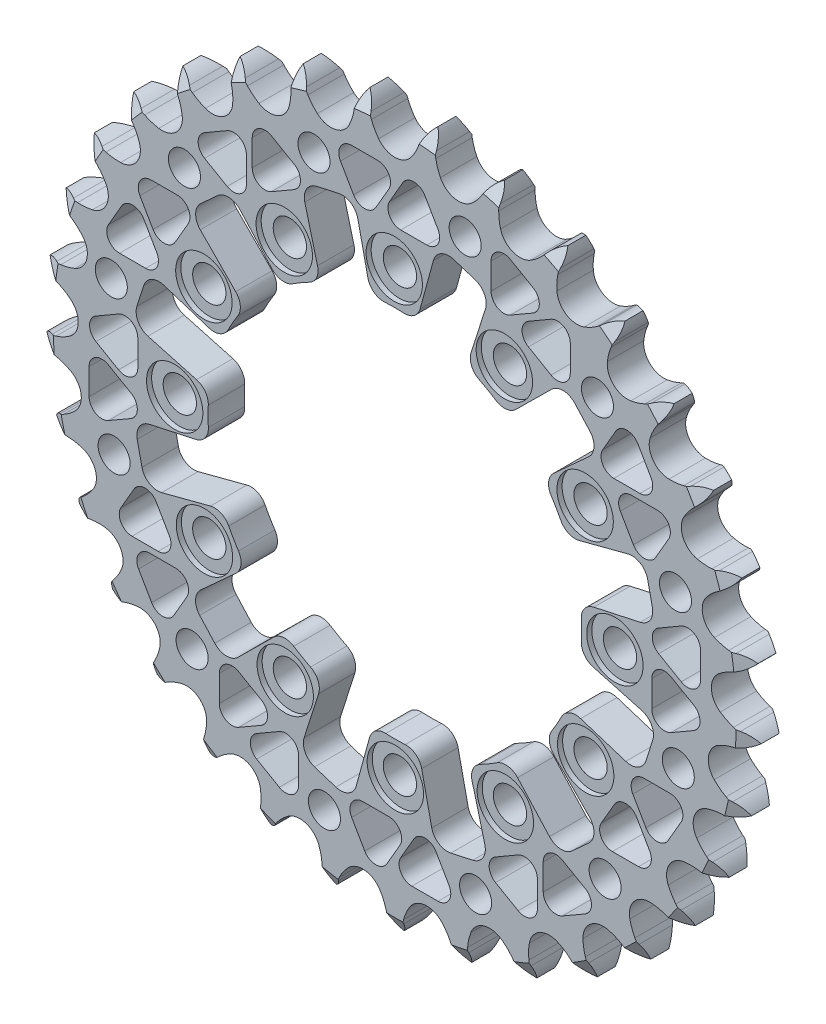
SolidWorks part; units mm, degrees
other "Markup1"
sketch "Sketch16" plane through (70.768, -70.8482, 7.2136) normal (0.1919, -0.04, 0.9806) x (0.9727, -0.1249, -0.1954)
material "7075-T6 (SN)"
ref_plane "Front Plane" through (0, 0, 0) normal (0, 0, 1) x (1, 0, 0)
ref_plane "Top Plane" through (0, 0, 0) normal (0, 1, 0) x (1, 0, 0)
ref_plane "Right Plane" through (0, 0, 0) normal (1, 0, 0) x (0, 0, -1)
sketch "Work Sketch" plane through (0, 0, 0) normal (0, 0, 1) x (1, 0, 0)
  line L0 (0, 0) -> (0, 160.4542) construction
  line L1 (-112.0919, 66.8027) -> (87.2579, 66.8027) construction
  line L2 (5.0834, 120.8822) -> (5.0834, 112.9699) construction
  line L3 (-12.8497, 70.6081) -> (16.7256, 70.6081) construction
  line L4 (5.0834, 70.6081) -> (-6.0658, 62.2619) construction
  line L5 (5.0834, 70.6081) -> (-4.6352, 66.9715) construction
  line L6 (-4.6352, 66.9715) -> (-6.998, 73.2861)
  line L7 (-11.5114, 65.7464) -> (-7.1525, 65.7464) construction
  line L8 (-11.0622, 124.7602) -> (-11.0622, 110.2345) construction
  line L9 (0, 0) -> (-4.0639, 42.5596) construction
  circle A0 centre (0, 0) radius 66.8027
  circle A1 centre (0, 66.8027) radius 4.0088
  arc A2 (-4.6352, 66.9715) -> (-3.2092, 64.4003) centre (5.0609, 70.6677) ccw
  circle A3 centre (-11.0622, 65.7464) radius 6.4488
  point P23 (-3.2092, 64.4003)
  dimension "D1" = 133.6054
  dimension "D8" = 10.3767
  dimension "D2" = 8.0177
  dimension "D3" = 5.0834
  dimension "D4" = 3.8054
  dimension "D5" = 36.818
  dimension "D6" = 16.303
  dimension "D7" = 10.3767
  dimension "D9" = 1.0563
  dimension "D10" = 11.0622
  dimension "D11" = 5.455
sketch "Teeth Sketch" plane through (0, 0, 0) normal (0, 0, 1) x (1, 0, 0)
  line L0 (5.0224, 68.0064) -> (4.6352, 66.9715)
  line L1 (-8.8439, 92.6176) -> (-5.6513, 59.1829) construction
  line L2 (0, 0) -> (-12.8498, 132.1321) construction
  line L3 (7.9387, 67.7279) -> (8.123, 66.6385)
  line L4 (19011.2087, -199094.3845) -> (-19015.2726, 199136.9441) construction
  line L5 (0, 146.3285) -> (0, 56.9858) construction
  line L6 (17.8019, 65.8269) -> (17.2258, 64.8841)
  line L7 (0, -200000) -> (0, 200160.4542) construction
  line L8 (20.6128, 65.0016) -> (20.5877, 63.897)
  line L9 (-4.6352, 66.9715) -> (-6.998, 73.2861) construction
  line L10 (43.2949, 52.6844) -> (42.861, 51.6682)
  line L11 (-5.0224, 68.0064) -> (-4.6352, 66.9715)
  line L12 (29.938, 61.2683) -> (29.1939, 60.4515)
  line L13 (32.5419, 59.9259) -> (32.3082, 58.846)
  line L14 (40.9921, 54.4953) -> (40.1069, 53.8341)
  line L15 (50.5647, 45.7527) -> (49.5703, 45.271)
  line L16 (52.4831, 43.5387) -> (51.8648, 42.623)
  line L17 (58.3096, 35.3565) -> (57.2421, 35.0716)
  line L18 (59.7744, 32.8194) -> (58.9939, 32.0373)
  line L19 (63.9472, 23.6824) -> (62.845, 23.6047)
  line L20 (64.9053, 20.9139) -> (63.9909, 20.2936)
  line L21 (67.2735, 11.1523) -> (66.1765, 11.2846)
  line L22 (67.6904, 8.2526) -> (66.6751, 7.8165)
  line L23 (68.1683, -1.7808) -> (67.1162, -1.4433)
  line L24 (68.0289, -4.7071) -> (66.9495, -4.9431)
  line L25 (66.5994, -14.6496) -> (65.6302, -14.119)
  line L26 (65.9088, -17.4966) -> (64.8042, -17.524)
  line L27 (62.6234, -26.9889) -> (61.7722, -26.2845)
  line L28 (61.4065, -29.6537) -> (60.3166, -29.4716)
  line L29 (56.3841, -38.3527) -> (55.6815, -37.4999)
  line L30 (54.6848, -40.739) -> (53.6491, -40.354)
  line L31 (48.1068, -48.3304) -> (47.5783, -47.3601)
  line L32 (45.9866, -50.352) -> (45.0425, -49.7779)
  line L33 (38.0909, -56.5613) -> (37.7556, -55.5085)
  line L34 (35.6264, -58.1451) -> (34.808, -57.4027)
  line L35 (26.6983, -62.7479) -> (26.5682, -61.6506)
  line L36 (23.9786, -63.8367) -> (23.3155, -62.9529)
  line L37 (14.3407, -66.6666) -> (14.4207, -65.5646)
  line L38 (11.4641, -67.221) -> (10.9802, -66.2277)
  line L39 (1.4648, -68.1759) -> (1.7519, -67.1089)
  line L40 (-1.4648, -68.1759) -> (-1.7519, -67.1089)
  line L41 (-11.4641, -67.221) -> (-10.9802, -66.2277)
  line L42 (-14.3407, -66.6666) -> (-14.4207, -65.5646)
  line L43 (-23.9786, -63.8367) -> (-23.3155, -62.9529)
  line L44 (-26.6983, -62.7479) -> (-26.5682, -61.6506)
  line L45 (-35.6264, -58.1451) -> (-34.808, -57.4027)
  line L46 (-38.0909, -56.5613) -> (-37.7556, -55.5085)
  line L47 (-45.9866, -50.352) -> (-45.0425, -49.7779)
  line L48 (-48.1068, -48.3304) -> (-47.5783, -47.3601)
  line L49 (-54.6848, -40.739) -> (-53.6491, -40.354)
  line L50 (-56.3841, -38.3527) -> (-55.6815, -37.4999)
  line L51 (-61.4065, -29.6537) -> (-60.3166, -29.4716)
  line L52 (-62.6234, -26.9889) -> (-61.7722, -26.2845)
  line L53 (-65.9088, -17.4966) -> (-64.8042, -17.524)
  line L54 (-66.5994, -14.6496) -> (-65.6302, -14.119)
  line L55 (-68.0289, -4.7071) -> (-66.9495, -4.9431)
  line L56 (-68.1683, -1.7808) -> (-67.1162, -1.4433)
  line L57 (-67.6904, 8.2526) -> (-66.6751, 7.8165)
  line L58 (-67.2735, 11.1523) -> (-66.1765, 11.2846)
  line L59 (-64.9053, 20.9139) -> (-63.9909, 20.2936)
  line L60 (-63.9472, 23.6824) -> (-62.845, 23.6047)
  line L61 (-59.7744, 32.8194) -> (-58.9939, 32.0373)
  line L62 (-58.3096, 35.3565) -> (-57.2421, 35.0716)
  line L63 (-52.4831, 43.5387) -> (-51.8648, 42.623)
  line L64 (-50.5647, 45.7527) -> (-49.5703, 45.271)
  line L65 (-43.2949, 52.6844) -> (-42.861, 51.6682)
  line L66 (-40.9921, 54.4953) -> (-40.1069, 53.8341)
  line L67 (-32.5419, 59.9259) -> (-32.3082, 58.846)
  line L68 (-29.938, 61.2683) -> (-29.1939, 60.4515)
  line L69 (-20.6128, 65.0016) -> (-20.5877, 63.897)
  line L70 (-17.8019, 65.8269) -> (-17.2258, 64.8841)
  line L71 (-7.9387, 67.7279) -> (-8.123, 66.6385)
  arc A0 (-6.8704, 70.647) -> (-5.0224, 68.0064) centre (-11.0622, 65.7464) cw
  circle A1 centre (-11.0622, 65.7464) radius 6.4488 construction
  arc A2 (-3.2092, 64.4003) -> (-4.6352, 66.9715) centre (5.0609, 70.6677) cw
  arc A3 (-4.6352, 66.9715) -> (-3.2092, 64.4003) centre (5.0609, 70.6677) ccw construction
  circle A4 centre (0, 66.8027) radius 4.0088 construction
  arc A5 (-3.2092, 64.4003) -> (3.2092, 64.4003) centre (0, 66.8027) ccw
  arc A6 (3.2092, 64.4003) -> (4.6352, 66.9715) centre (-5.0609, 70.6677) ccw
  arc A7 (6.8704, 70.647) -> (5.0224, 68.0064) centre (11.0622, 65.7464) ccw
  arc A8 (6.6238, 70.6705) -> (7.9387, 67.7279) centre (1.5803, 66.6518) cw
  arc A9 (9.0366, 63.8438) -> (8.123, 66.6385) centre (18.3434, 68.4328) cw
  arc A10 (9.0366, 63.8438) -> (15.3391, 62.6291) centre (12.6425, 65.5955) ccw
  arc A11 (15.3391, 62.6291) -> (17.2258, 64.8841) centre (8.4044, 70.3484) ccw
  arc A12 (20.1163, 68.0701) -> (17.8019, 65.8269) centre (23.3049, 62.4647) ccw
  arc A13 (19.8786, 68.1399) -> (20.6128, 65.0016) centre (14.1657, 65.1482) cw
  arc A14 (20.9558, 60.9799) -> (20.5877, 63.897) centre (30.9629, 63.7246) cw
  arc A15 (20.9558, 60.9799) -> (26.9145, 58.5944) centre (24.8281, 62.0175) ccw
  arc A16 (26.9145, 58.5944) -> (29.1939, 60.4515) centre (21.5661, 67.4865) ccw
  arc A17 (32.6351, 63.0329) -> (29.938, 61.2683) centre (34.7052, 56.9254) ccw
  arc A18 (32.4149, 63.1465) -> (32.5419, 59.9259) centre (26.2391, 61.29) cw
  arc A19 (32.1176, 55.912) -> (32.3082, 58.846) centre (42.4634, 56.7133) cw
  arc A20 (32.1176, 55.912) -> (37.5172, 52.4419) centre (36.1163, 56.198) ccw
  arc A21 (37.5172, 52.4419) -> (40.1069, 53.8341) centre (33.9483, 62.1856) ccw
  arc A22 (43.9744, 55.7176) -> (40.9921, 54.4953) centre (44.8513, 49.3287) ccw
  arc A23 (43.7796, 55.8708) -> (43.2949, 52.6844) centre (37.3641, 55.2167) cw
  arc A24 (42.1187, 48.8233) -> (42.861, 51.6682) centre (52.429, 47.6521) cw
  arc A25 (42.1187, 48.8233) -> (46.7639, 44.3941) centre (46.0991, 48.3474) ccw
  arc A26 (46.7639, 44.3941) -> (49.5703, 45.271) centre (45.1035, 54.637) ccw
  arc A27 (53.7244, 46.3885) -> (50.5647, 45.7527) centre (53.3763, 39.9491) ccw
  arc A28 (53.5621, 46.5757) -> (52.4831, 43.5387) centre (47.1387, 47.1476) cw
  arc A29 (50.5974, 39.97) -> (51.8648, 42.623) centre (60.4998, 36.8687) cw
  arc A30 (50.5974, 39.97) -> (54.3205, 34.7417) centre (54.4159, 38.7494) ccw
  arc A31 (54.3205, 34.7417) -> (57.2421, 35.0716) centre (54.6285, 45.1138) ccw
  arc A32 (61.5326, 35.3828) -> (58.3096, 35.3565) centre (59.9721, 29.1257) ccw
  arc A33 (61.4087, 35.5974) -> (59.7744, 32.8194) centre (55.2096, 37.3746) cw
  arc A34 (57.2474, 29.6721) -> (58.9939, 32.0373) centre (66.384, 24.7528) cw
  arc A35 (57.2474, 29.6721) -> (59.9137, 23.8336) centre (60.7659, 27.7508) ccw
  arc A36 (59.9137, 23.8336) -> (62.845, 23.6047) centre (62.1792, 33.96) ccw
  arc A37 (67.1168, 23.0983) -> (63.9472, 23.6824) centre (64.4004, 17.2495) ccw
  arc A38 (67.0358, 23.3324) -> (64.9053, 20.9139) centre (61.2851, 26.2507) cw
  arc A39 (61.8283, 18.3017) -> (63.9909, 20.2936) centre (69.8688, 11.7422) cw
  arc A40 (61.8283, 18.3017) -> (63.3416, 12.0642) centre (64.9196, 15.7493) ccw
  arc A41 (63.3416, 12.0642) -> (66.1765, 11.2846) centre (67.4825, 21.5788) ccw
  arc A42 (70.2753, 9.9789) -> (67.2735, 11.1523) centre (66.5011, 4.7499) ccw
  arc A43 (70.2401, 10.2242) -> (67.6904, 8.2526) centre (65.1456, 14.178) cw
  arc A44 (64.1746, 6.2699) -> (66.6751, 7.8165) centre (70.8284, -1.6927) cw
  arc A45 (64.1746, 6.2699) -> (64.48, -0.1413) centre (66.727, 3.1786) ccw
  arc A46 (64.48, -0.1413) -> (67.1162, -1.4433) centre (70.3468, 8.4177) ccw
  arc A47 (70.8939, -3.5011) -> (68.1683, -1.7808) centre (66.1983, -7.9213) ccw
  arc A48 (70.9057, -3.2536) -> (68.0289, -4.7071) centre (66.6515, 1.5929) cw
  arc A49 (64.2015, -5.9885) -> (66.9495, -4.9431) centre (69.2281, -15.0665) cw
  arc A50 (64.2015, -5.9885) -> (63.2881, -12.3417) centre (66.1227, -9.507) ccw
  arc A51 (63.2881, -12.3417) -> (65.6302, -14.119) centre (70.6686, -5.0476) ccw
  arc A52 (68.9501, -16.8546) -> (66.5994, -14.6496) centre (63.5029, -20.3063) ccw
  arc A53 (69.0085, -16.6138) -> (65.9088, -17.4966) centre (65.7485, -11.0498) cw
  arc A54 (61.908, -18.0305) -> (64.8042, -17.524) centre (65.1257, -27.8957) cw
  arc A55 (61.908, -18.0305) -> (59.8087, -24.096) centre (63.1286, -21.849) ccw
  arc A56 (59.8087, -24.096) -> (61.7722, -26.2845) centre (68.4363, -18.3305) ccw
  arc A57 (64.5144, -29.5989) -> (62.6234, -26.9889) centre (58.5123, -31.9573) ccw
  arc A58 (64.6173, -29.3735) -> (61.4065, -29.6537) centre (62.4691, -23.2931) cw
  arc A59 (57.3769, -29.4209) -> (60.3166, -29.4716) centre (58.6695, -39.7167) cw
  arc A60 (57.3769, -29.4209) -> (54.1677, -34.9794) centre (57.8528, -33.4013) ccw
  arc A61 (54.1677, -34.9794) -> (55.6815, -37.4999) centre (63.7305, -30.9509) ccw
  arc A62 (57.7469, -41.2734) -> (56.3841, -38.3527) centre (51.4069, -42.4533) ccw
  arc A63 (57.8906, -41.0716) -> (54.6848, -40.739) centre (56.932, -34.6945) cw
  arc A64 (50.7721, -39.7478) -> (53.6491, -40.354) centre (50.0928, -50.1023) cw
  arc A65 (50.7721, -39.7478) -> (46.5689, -44.5986) centre (50.4861, -43.7465) ccw
  arc A66 (46.5689, -44.5986) -> (47.5783, -47.3601) centre (56.7213, -42.4527) ccw
  arc A67 (48.8923, -51.4562) -> (48.1068, -48.3304) centre (42.4436, -51.415) ccw
  arc A68 (49.0716, -51.2853) -> (45.9866, -50.352) centre (49.3372, -44.842) cw
  arc A69 (42.3322, -48.6382) -> (45.0425, -49.7779) centre (39.7057, -58.677) cw
  arc A70 (42.3322, -48.6382) -> (37.287, -52.6059) centre (41.2947, -52.5105) ccw
  arc A71 (37.287, -52.6059) -> (37.7556, -55.5085) centre (47.662, -52.4201) ccw
  arc A72 (38.2706, -59.7793) -> (38.0909, -56.5613) centre (31.9463, -58.5183) ccw
  arc A73 (38.479, -59.6453) -> (35.6264, -58.1451) centre (39.9592, -53.3687) cw
  arc A74 (32.3624, -55.7707) -> (34.808, -57.4027) centre (27.8834, -65.131) cw
  arc A75 (32.3624, -55.7707) -> (26.6574, -58.7118) centre (30.6108, -59.3766) ccw
  arc A76 (26.6574, -58.7118) -> (26.5682, -61.6506) centre (36.8801, -60.4929) ccw
  arc A77 (26.2657, -65.9417) -> (26.6983, -62.7479) centre (20.2943, -63.5067) ccw
  arc A78 (26.4957, -65.8497) -> (23.9786, -63.8367) centre (29.137, -59.9666) cw
  arc A79 (21.2229, -60.8875) -> (23.3155, -62.9529) centre (15.0534, -69.2309) cw
  arc A80 (21.2229, -60.8875) -> (15.0644, -62.6958) centre (18.8205, -64.0967) ccw
  arc A81 (15.0644, -62.6958) -> (14.4207, -65.5646) centre (24.7653, -66.3793) ccw
  arc A82 (13.3114, -69.7209) -> (14.3407, -66.6666) centre (7.9088, -66.1998) ccw
  arc A83 (13.5547, -69.674) -> (11.4641, -67.221) centre (17.2617, -64.3972) cw
  arc A84 (9.3163, -63.8036) -> (10.9802, -66.2277) centre (1.6794, -70.8287) cw
  arc A85 (9.3163, -63.8036) -> (2.9269, -64.4137) centre (6.35, -66.5002) ccw
  arc A86 (2.9269, -64.4137) -> (1.7519, -67.1089) centre (11.7554, -69.8666) ccw
  arc A87 (-0.1239, -70.9802) -> (1.4648, -68.1759) centre (-4.7625, -66.5002) ccw
  arc A88 (0.1239, -70.9802) -> (-1.4648, -68.1759) centre (4.7625, -66.5002) cw
  arc A89 (-2.9269, -64.4137) -> (-1.7519, -67.1089) centre (-11.7554, -69.8666) cw
  arc A90 (-2.9269, -64.4137) -> (-9.3163, -63.8036) centre (-6.35, -66.5002) ccw
  arc A91 (-9.3163, -63.8036) -> (-10.9802, -66.2277) centre (-1.6794, -70.8287) ccw
  arc A92 (-13.5547, -69.674) -> (-11.4641, -67.221) centre (-17.2617, -64.3972) ccw
  arc A93 (-13.3114, -69.7209) -> (-14.3407, -66.6666) centre (-7.9088, -66.1998) cw
  arc A94 (-15.0644, -62.6958) -> (-14.4207, -65.5646) centre (-24.7653, -66.3793) cw
  arc A95 (-15.0644, -62.6958) -> (-21.2229, -60.8875) centre (-18.8205, -64.0967) ccw
  arc A96 (-21.2229, -60.8875) -> (-23.3155, -62.9529) centre (-15.0534, -69.2309) ccw
  arc A97 (-26.4957, -65.8497) -> (-23.9786, -63.8367) centre (-29.137, -59.9666) ccw
  arc A98 (-26.2657, -65.9417) -> (-26.6983, -62.7479) centre (-20.2943, -63.5067) cw
  arc A99 (-26.6574, -58.7118) -> (-26.5682, -61.6506) centre (-36.8801, -60.4929) cw
  arc A100 (-26.6574, -58.7118) -> (-32.3624, -55.7707) centre (-30.6108, -59.3766) ccw
  arc A101 (-32.3624, -55.7707) -> (-34.808, -57.4027) centre (-27.8834, -65.131) ccw
  arc A102 (-38.479, -59.6453) -> (-35.6264, -58.1451) centre (-39.9592, -53.3687) ccw
  arc A103 (-38.2706, -59.7793) -> (-38.0909, -56.5613) centre (-31.9463, -58.5183) cw
  arc A104 (-37.287, -52.6059) -> (-37.7556, -55.5085) centre (-47.662, -52.4201) cw
  arc A105 (-37.287, -52.6059) -> (-42.3322, -48.6382) centre (-41.2947, -52.5105) ccw
  arc A106 (-42.3322, -48.6382) -> (-45.0425, -49.7779) centre (-39.7057, -58.677) ccw
  arc A107 (-49.0716, -51.2853) -> (-45.9866, -50.352) centre (-49.3372, -44.842) ccw
  arc A108 (-48.8923, -51.4562) -> (-48.1068, -48.3304) centre (-42.4436, -51.415) cw
  arc A109 (-46.5689, -44.5986) -> (-47.5783, -47.3601) centre (-56.7213, -42.4527) cw
  arc A110 (-46.5689, -44.5986) -> (-50.7721, -39.7478) centre (-50.4861, -43.7465) ccw
  arc A111 (-50.7721, -39.7478) -> (-53.6491, -40.354) centre (-50.0928, -50.1023) ccw
  arc A112 (-57.8906, -41.0716) -> (-54.6848, -40.739) centre (-56.932, -34.6945) ccw
  arc A113 (-57.7469, -41.2734) -> (-56.3841, -38.3527) centre (-51.4069, -42.4533) cw
  arc A114 (-54.1677, -34.9794) -> (-55.6815, -37.4999) centre (-63.7305, -30.9509) cw
  arc A115 (-54.1677, -34.9794) -> (-57.3769, -29.4209) centre (-57.8528, -33.4013) ccw
  arc A116 (-57.3769, -29.4209) -> (-60.3166, -29.4716) centre (-58.6695, -39.7167) ccw
  arc A117 (-64.6173, -29.3735) -> (-61.4065, -29.6537) centre (-62.4691, -23.2931) ccw
  arc A118 (-64.5144, -29.5989) -> (-62.6234, -26.9889) centre (-58.5123, -31.9573) cw
  arc A119 (-59.8087, -24.096) -> (-61.7722, -26.2845) centre (-68.4363, -18.3305) cw
  arc A120 (-59.8087, -24.096) -> (-61.908, -18.0305) centre (-63.1286, -21.849) ccw
  arc A121 (-61.908, -18.0305) -> (-64.8042, -17.524) centre (-65.1257, -27.8957) ccw
  arc A122 (-69.0085, -16.6138) -> (-65.9088, -17.4966) centre (-65.7485, -11.0498) ccw
  arc A123 (-68.9501, -16.8546) -> (-66.5994, -14.6496) centre (-63.5029, -20.3063) cw
  arc A124 (-63.2881, -12.3417) -> (-65.6302, -14.119) centre (-70.6686, -5.0476) cw
  arc A125 (-63.2881, -12.3417) -> (-64.2015, -5.9885) centre (-66.1227, -9.507) ccw
  arc A126 (-64.2015, -5.9885) -> (-66.9495, -4.9431) centre (-69.2281, -15.0665) ccw
  arc A127 (-70.9057, -3.2536) -> (-68.0289, -4.7071) centre (-66.6515, 1.5929) ccw
  arc A128 (-70.8939, -3.5011) -> (-68.1683, -1.7808) centre (-66.1983, -7.9213) cw
  arc A129 (-64.48, -0.1413) -> (-67.1162, -1.4433) centre (-70.3468, 8.4177) cw
  arc A130 (-64.48, -0.1413) -> (-64.1746, 6.2699) centre (-66.727, 3.1786) ccw
  arc A131 (-64.1746, 6.2699) -> (-66.6751, 7.8165) centre (-70.8284, -1.6927) ccw
  arc A132 (-70.2401, 10.2242) -> (-67.6904, 8.2526) centre (-65.1456, 14.178) ccw
  arc A133 (-70.2753, 9.9789) -> (-67.2735, 11.1523) centre (-66.5011, 4.7499) cw
  arc A134 (-63.3416, 12.0642) -> (-66.1765, 11.2846) centre (-67.4825, 21.5788) cw
  arc A135 (-63.3416, 12.0642) -> (-61.8283, 18.3017) centre (-64.9196, 15.7493) ccw
  arc A136 (-61.8283, 18.3017) -> (-63.9909, 20.2936) centre (-69.8688, 11.7422) ccw
  arc A137 (-67.0358, 23.3324) -> (-64.9053, 20.9139) centre (-61.2851, 26.2507) ccw
  arc A138 (-67.1168, 23.0983) -> (-63.9472, 23.6824) centre (-64.4004, 17.2495) cw
  arc A139 (-59.9137, 23.8336) -> (-62.845, 23.6047) centre (-62.1792, 33.96) cw
  arc A140 (-59.9137, 23.8336) -> (-57.2474, 29.6721) centre (-60.7659, 27.7508) ccw
  arc A141 (-57.2474, 29.6721) -> (-58.9939, 32.0373) centre (-66.384, 24.7528) ccw
  arc A142 (-61.4087, 35.5974) -> (-59.7744, 32.8194) centre (-55.2096, 37.3746) ccw
  arc A143 (-61.5326, 35.3828) -> (-58.3096, 35.3565) centre (-59.9721, 29.1257) cw
  arc A144 (-54.3205, 34.7417) -> (-57.2421, 35.0716) centre (-54.6285, 45.1138) cw
  arc A145 (-54.3205, 34.7417) -> (-50.5974, 39.97) centre (-54.4159, 38.7494) ccw
  arc A146 (-50.5974, 39.97) -> (-51.8648, 42.623) centre (-60.4998, 36.8687) ccw
  arc A147 (-53.5621, 46.5757) -> (-52.4831, 43.5387) centre (-47.1387, 47.1476) ccw
  arc A148 (-53.7244, 46.3885) -> (-50.5647, 45.7527) centre (-53.3763, 39.9491) cw
  arc A149 (-46.7639, 44.3941) -> (-49.5703, 45.271) centre (-45.1035, 54.637) cw
  arc A150 (-46.7639, 44.3941) -> (-42.1187, 48.8233) centre (-46.0991, 48.3474) ccw
  arc A151 (-42.1187, 48.8233) -> (-42.861, 51.6682) centre (-52.429, 47.6521) ccw
  arc A152 (-43.7796, 55.8708) -> (-43.2949, 52.6844) centre (-37.3641, 55.2167) ccw
  arc A153 (-43.9744, 55.7176) -> (-40.9921, 54.4953) centre (-44.8513, 49.3287) cw
  arc A154 (-37.5172, 52.4419) -> (-40.1069, 53.8341) centre (-33.9483, 62.1856) cw
  arc A155 (-37.5172, 52.4419) -> (-32.1176, 55.912) centre (-36.1163, 56.198) ccw
  arc A156 (-32.1176, 55.912) -> (-32.3082, 58.846) centre (-42.4634, 56.7133) ccw
  arc A157 (-32.4149, 63.1465) -> (-32.5419, 59.9259) centre (-26.2391, 61.29) ccw
  arc A158 (-32.6351, 63.0329) -> (-29.938, 61.2683) centre (-34.7052, 56.9254) cw
  arc A159 (-26.9145, 58.5944) -> (-29.1939, 60.4515) centre (-21.5661, 67.4865) cw
  arc A160 (-26.9145, 58.5944) -> (-20.9558, 60.9799) centre (-24.8281, 62.0175) ccw
  arc A161 (-20.9558, 60.9799) -> (-20.5877, 63.897) centre (-30.9629, 63.7246) ccw
  arc A162 (-19.8786, 68.1399) -> (-20.6128, 65.0016) centre (-14.1657, 65.1482) ccw
  arc A163 (-20.1163, 68.0701) -> (-17.8019, 65.8269) centre (-23.3049, 62.4647) cw
  arc A164 (-15.3391, 62.6291) -> (-17.2258, 64.8841) centre (-8.4044, 70.3484) cw
  arc A165 (-15.3391, 62.6291) -> (-9.0366, 63.8438) centre (-12.6425, 65.5955) ccw
  arc A166 (-9.0366, 63.8438) -> (-8.123, 66.6385) centre (-18.3434, 68.4328) ccw
  arc A167 (-6.6238, 70.6705) -> (-7.9387, 67.7279) centre (-1.5803, 66.6518) ccw
  point P77 (0, 0)
  dimension "D1" = 5.455
  dimension "D2" = 5.555
  dimension "D3" = 33
extrude "Extrusion" add sketch "Teeth Sketch" along normal blind 7.2136
hole_wizard "M6 Clearance Hole1" positions "Sketch6" profile "Sketch7" hole size "M6" standard "ANSI Metric"
sketch "Sketch6" plane through (0, 0, 0) normal (0, 0, -1) x (-1, 0, 0)
  circle A0 centre (0, 0) radius 43.5
  point P0 (0, 43.5)
  dimension "D1" = 87
sketch "Sketch7" plane through (0, 43.5, 0) normal (1, 0, 0) x (0, 1, 0)
  line L0 (0, 0) -> (0, 19.2548)
  line L1 (0, 19.2548) -> (3.3, 17.272)
  line L2 (3.3, 17.272) -> (3.3, 0)
  line L5 (3.3, 0) -> (0, 0)
  line L10 (0, 19.2548) -> (-3.3, 17.272) construction
  line L11 (0, -6.35) -> (0, 107.95) construction
  dimension "Hole Dia." = 6.6
  dimension "Hole Depth" = 17.272
  dimension "Drill Angle" = 118
pattern_circular "CirPattern1" count 12 over 360 about axis through (0, -0.1107, 0) along (0, 0, 1) of "M6 Clearance Hole1"
sketch "Sketch8" plane through (0, 0, 0) normal (0, 0, -1) x (-1, 0, 0)
  circle A0 centre (0, 0) radius 37
  dimension "D1" = 74
extrude "Cut-Extrude1" cut sketch "Sketch8" against normal through all both and the other way through all
ref_plane "Sprocket Center Plane" through (0, 0, 3.6068) normal (0, 0, 1) x (1, 0, 0)
sketch "Pitch Circle" plane through (0, 0, 3.6068) normal (0, 0, -1) x (-1, 0, 0)
  circle A0 centre (0, 0) radius 66.8027 construction
  dimension "D1" = 133.6054
ref_plane "Center Plane" through (0, 0, 3.6068) normal (0, 0, 1) x (1, 0, 0)
ref_axis "Axis1" through (0, 0, 7.2136) along (0, 0, -1)
sketch "Sketch5" plane through (0, 0, 0) normal (1, 0, 0) x (0, 0, -1)
  line L0 (-1.8288, -70.8482) -> (-5.3848, -70.8482)
  line L1 (-7.2136, -51.2753) -> (0, -51.2753) construction
  line L2 (-5.3848, -70.8482) -> (-5.3848, -67.6547)
  line L3 (-5.3848, -67.6547) -> (-7.2136, -67.6547)
  line L4 (-7.2136, -67.6547) -> (-5.3848, -70.8482)
  line L5 (-7.2136, -67.6547) -> (-7.2136, -70.8482)
  line L6 (-7.2136, -70.8482) -> (-5.3848, -70.8482)
  line L8 (-7.2136, -70.8482) -> (0, -70.8482) construction
  line L9 (-7.2136, -68.1759) -> (-7.2136, -70.8482) construction
  dimension "D1" = 3.556
  dimension "D2" = 3.1936
  dimension "D3" = 1.8288
revolve "Cut-Revolve1" cut sketch "Sketch5" angle 360 about axis through (0, 0, 7.2136) along (0, 0, -1)
mirror "Mirror1" about plane through (0, 0, 3.6068) normal (0, 0, 1) of "Cut-Revolve1"
sketch "Sketch10" plane through (0, 0, 0) normal (0, 0, 1) x (1, 0, 0)
  line L0 (0, 0) -> (-79.643, -0.2022) construction
  line L1 (0, 0) -> (-79.6429, 10.0842) construction
  line L2 (0, 0) -> (-79.643, -10.4954) construction
  line L3 (-59.2423, 9.0305) -> (-51.4071, 1.075)
  line L5 (-49.1987, 6.2294) -> (-49.1987, 5.0699)
  line L6 (-51.4071, 1.075) -> (-62.5732, 1.075)
  line L8 (-62.7341, -1.6349) -> (-51.5692, -1.4798)
  line L9 (-51.5692, -1.4798) -> (-59.2931, -9.5434)
  line L12 (-49.1987, -0.1249) -> (-49.1987, -0.1107)
  line L15 (-51.5692, -1.4798) -> (-53.764, -1.4798) construction
  line L16 (-51.4071, 1.075) -> (-52.3044, 1.075) construction
  line L17 (-59.2423, 9.0305) -> (-62.5732, 1.075)
  line L18 (-62.7341, -1.6349) -> (-59.2931, -9.5434)
  line L19 (-45.388, 21.6946) -> (-49.1987, 5.0699)
  line L20 (-31.807, 16.9479) -> (-36.0091, 0.4177)
  line L22 (-49.1987, -0.1107) -> (-49.1987, -0.1249)
  line L23 (-49.1987, 5.0699) -> (-49.1987, 6.2294)
  circle A0 centre (-43.6107, -0.1107) radius 5.588
  circle A1 centre (-37.768, 21.6946) radius 5.588
  arc A2 (-36.0091, 0.4177) -> (-49.1987, 5.0699) centre (-43.6107, -0.1107) ccw
  arc A3 (-45.388, 21.6946) -> (-31.807, 16.9479) centre (-37.768, 21.6946) ccw
  dimension "D1" = 11.176
  dimension "D12" = 15.24
  dimension "D2" = 4.8001
  dimension "D3" = 0.7635
  dimension "D4" = 35.8718
  dimension "D6" = 11.165
  dimension "D8" = 2.7099
  dimension "D10" = 11.166
  dimension "D11" = 7.9555
  dimension "D13" = 35.0021
extrude "Cut-Extrude2" cut sketch "Sketch10" against normal blind 1.016 from surface at 7.2136 contours A0 starting at face at (-37, 0, 7.2136)
pattern_circular "CirPattern2" count 12 over 360 about axis through (0, 0, 0) along (0, 0, 1) of "Cut-Extrude2"
ref_plane "Half Plane" through (0, 0, 3.6068) normal (0, 0, 1) x (1, 0, 0)
sketch "Motor Shaft Sprocket Dimensions" plane through (0, 0, 3.6068) normal (0, 0, 1) x (1, 0, 0)
  line L0 (0, 0) -> (-177.8, 0)
  line L1 (-177.8, 0) -> (-177.8, 23.6982)
  line L2 (-180.2273, 51.0991) -> (-5.8945, 66.5421)
  line L3 (-187.3193, -2.1104) -> (-23.1174, -62.6753)
  line L4 (-5.8945, 66.5421) -> (0, 0)
  line L5 (0, 0) -> (-23.1174, -62.6753)
  circle A0 centre (-177.8, 23.6982) radius 27.5082
  circle A1 centre (0, 0) radius 66.8027 construction
  dimension "D3" = 55.0164
  dimension "D1" = 177.8
  dimension "D2" = 23.6982
  dimension "D4" = 205.308
sketch "Sketch12" plane through (0, 0, 7.2136) normal (0, 0, 1) x (1, 0, 0)
  line L4 (7.6486, 48.9178) -> (4.8815, 38.8262)
  line L5 (7.1039, 34.9247) -> (10.9687, 33.865)
  line L10 (14.8328, 35.9612) -> (17.9625, 45.7626)
  line L11 (15.9037, 49.7529) -> (11.6763, 51.1027)
  arc A1 (4.8815, 38.8262) -> (7.1039, 34.9247) centre (7.9435, 37.9866) ccw
  arc A2 (10.9687, 33.865) -> (14.8328, 35.9612) centre (11.8083, 36.927) ccw
  arc A3 (17.9625, 45.7626) -> (15.9037, 49.7529) centre (14.9379, 46.7284) ccw
  arc A4 (11.6763, 51.1027) -> (7.6486, 48.9178) centre (10.7106, 48.0782) ccw
  point P8 (13.9063, 33.0595)
  point P11 (18.9282, 48.7872)
  point P14 (8.5237, 52.1094)
  dimension "D3" = 3.175
  dimension "D7" = 36.927
  dimension "D1" = 10.922
  dimension "D2" = 16.51
  dimension "D4" = 35.56
  dimension "D5" = 5.5593
  dimension "D6" = 52.2329
extrude "Cut-Extrude5" cut sketch "Sketch12" against normal up to next
pattern_circular "CirPattern3" count 12 over 360 about axis through (0, 0, 0) along (0, 0, 1) of "Cut-Extrude5"
sketch "Sketch13" plane through (0, 0, 7.2136) normal (0, 0, 1) x (1, 0, 0)
  line L0 (-10.7537, 56.7643) -> (-8.1681, 52.2859)
  line L1 (-3.7687, 52.2859) -> (-1.1831, 56.7643)
  line L2 (-3.3828, 60.5743) -> (-8.554, 60.5743)
  line L3 (-1.0221, 54.7302) -> (1.5635, 59.2085)
  line L4 (5.9629, 59.2085) -> (8.5485, 54.7302)
  line L5 (6.3488, 50.9202) -> (1.1776, 50.9202)
  arc A0 (6.3488, 50.9202) -> (8.5485, 54.7302) centre (6.3488, 53.4602) ccw
  arc A1 (1.1776, 50.9202) -> (-1.0221, 54.7302) centre (1.1776, 53.4602) cw
  arc A2 (5.9629, 59.2085) -> (1.5635, 59.2085) centre (3.7632, 57.9385) ccw
  arc A3 (-10.7537, 56.7643) -> (-8.554, 60.5743) centre (-8.554, 58.0343) cw
  arc A4 (-3.7687, 52.2859) -> (-8.1681, 52.2859) centre (-5.9684, 53.5559) cw
  arc A5 (-3.3828, 60.5743) -> (-1.1831, 56.7643) centre (-3.3828, 58.0343) cw
  point P15 (-12.9534, 60.5743)
  point P18 (-5.9684, 48.4759)
  dimension "D2" = 2.54
  dimension "D5" = 58.0343
  dimension "D6" = 28.2502
  dimension "D1" = 13.97
  dimension "D3" = 19.0691
  dimension "D4" = 57.9385
extrude "Cut-Extrude7" cut sketch "Sketch13" against normal up to next
pattern_circular "CirPattern4" count 12 over 360 about axis through (0, 0, 0) along (0, 0, 1) of "Cut-Extrude7"
fillet "Fillet1" radius 3.175 24 edges at (5.327, -36.6145, 3.6068) (-5.0627, -36.652, 3.6068) (22.9206, -29.0456, 3.6068) (13.9416, -34.2729, 3.6068) (29.2102, -22.7104, 3.6068) (34.3726, -13.694, 3.6068) (36.652, -5.0627, 3.6068) (36.6145, 5.327, 3.6068) (29.0456, 22.9206, 3.6068) (34.2729, 13.9416, 3.6068) (-13.694, -34.3726, 3.6068) (-22.7104, -29.2102, 3.6068) (-29.0456, -22.9206, 3.6068) (-34.2729, -13.9416, 3.6068) (-36.6145, -5.327, 3.6068) (-36.652, 5.0627, 3.6068) (-34.3726, 13.694, 3.6068) (-29.2102, 22.7104, 3.6068) (-22.9206, 29.0456, 3.6068) (-5.327, 36.6145, 3.6068) (-13.9416, 34.2729, 3.6068) (5.0627, 36.652, 3.6068) (13.694, 34.3726, 3.6068) (22.7104, 29.2102, 3.6068)
sketch "Sketch14" plane through (0, 0, 7.2136) normal (0, 0, 1) x (1, 0, 0)
  line L0 (-20.4232, 54.3508) -> (-17.561, 51.6999)
  line L1 (-13.3583, 53.0005) -> (-12.4936, 56.8046)
  line L2 (-15.7213, 59.7941) -> (-19.4481, 58.6408)
  arc A0 (-13.3583, 53.0005) -> (-17.561, 51.6999) centre (-15.8351, 53.5634) cw
  arc A1 (-12.4936, 56.8046) -> (-15.7213, 59.7941) centre (-14.9704, 57.3676) ccw
  arc A2 (-19.4481, 58.6408) -> (-20.4232, 54.3508) centre (-18.6973, 56.2143) ccw
  point P2 (-13.4332, 62.2249)
  point P8 (-11.5185, 61.0946)
  point P11 (-23.6509, 57.3402)
  dimension "D2" = 2.54
  dimension "D1" = 12.7
  dimension "D3" = 24.773
  dimension "D4" = 57.3676
  dimension "D5" = 25.9977
extrude "Cut-Extrude8" [suppressed] cut sketch "Sketch14" against normal up to next
pattern_circular "CirPattern5" [suppressed] count 12 over 360
hole_wizard "1/4 (0.2500) Dowel Hole1" positions "3DSketch1" profile "Sketch15" hole size "1/4" standard "ANSI Inch" end condition up to next
sketch3d "3DSketch1"
  circle A0 centre (-0.1107, 43.6107, 7.2136) radius 5.588 construction
  point P0 (13.9416, 56.1687, 7.2136)
  point P4 (-0.1107, 43.6107, 12.8016)
  dimension "D1" = 58.321
  dimension "D2" = 18.846
sketch "Sketch15" plane through (13.9416, 56.1687, 7.2136) normal (1, 0, 0) x (0, -1, 0)
  line L0 (0, 0) -> (0, 7.2136)
  line L1 (0, 7.2136) -> (3.175, 7.2136)
  line L2 (3.175, 7.2136) -> (3.175, 0)
  line L5 (3.175, 0) -> (0, 0)
  line L11 (0, -6.35) -> (0, 107.95) construction
  dimension "Thru Hole Dia." = 6.35
  dimension "Thru Hole Depth" = 7.2136
pattern_circular "CirPattern6" count 12 over 360 about axis through (0, 0, 0) along (0, 0, 1) of "1/4 (0.2500) Dowel Hole1"
equation "\"P\"= 0.500'//Chain Pitch"
equation "\"N\"= 33'//Number of Teeth"
equation "\"Dr\"= 5 / 16'//Roller Diameter"
equation "\"Ds\"= 1.0005 * \"Dr\" + 0.003'Seating Curve DIameter"
equation "\"R\"= \"Ds\" / 2"
equation "\"A\"= 35 + 60 / \"N\""
equation "\"B\"= 18 - 56 / \"N\""
equation "\"ac\"= 0.8 * \"Dr\""
equation "\"M\"= 0.8 * \"Dr\" * cos ( 35 + 60 / \"N\" )"
equation "\"T\"= 0.8 * \"Dr\" * sin ( 35 + 60 / \"N\" )"
equation "\"E\"= 1.3025 * \"Dr\" + 0.0015"
equation "\"Chordal Length of Arc xy\"= ( 2.605 * \"Dr\" + 0.003 ) * sin ( 9 - 28 / \"N\" )"
equation "\"yz\"= \"Dr\" * ( 1.4 * sin ( 17 - 64 / \"N\" ) - 0.8 * sin ( 18 - 56 / \"N\" ) )"
equation "\"ab\"= 1.4 * \"Dr\""
equation "\"W\"= 1.4 * \"Dr\" * cos ( 180 / \"N\" )"
equation "\"V\"= 1.4 * \"Dr\" * sin ( 180 / \"N\" )"
equation "\"F\"= \"Dr\" * ( 0.8 * cos ( 18 - 56 / \"N\" ) + 1.4 * cos ( 17 - 64 / \"N\" ) - 1.3025 )"
equation "\"H\"= sqr ( \"F\" ^ 2 - ( 1.4 * \"Dr\" - \"P\" / 2 ) ^ 2 )"
equation "\"S\"= \"P\" / 2 * cos ( 180 / \"N\" ) + \"H\" * sin ( 180 / \"N\" )"
equation "\"PD\"= \"P\" / ( sin ( 180 / \"N\" ) )"
equation "\"D1@Work Sketch\" = \"PD\""
equation "\"D3@Work Sketch\" = \"M\""
equation "\"D4@Work Sketch\" = \"T\""
equation "\"D5@Work Sketch\" = \"A\""
equation "\"D6@Work Sketch\" = \"B\""
equation "\"D7@Work Sketch\" = \"E\""
equation "\"D8@Work Sketch\" = \"E\""
equation "\"D9@Work Sketch\" = \"V\""
equation "\"D10@Work Sketch\" = \"W\""
equation "\"D2@Work Sketch\" = \"R\" * 2"
equation "\"D11@Work Sketch\" = 180 / \"N\""
equation "\"D2@Teeth Sketch\" = 180 / \"N\" + 0.1"
equation "\"D3@Teeth Sketch\" = \"N\""
equation "\"Edge Thickness\"=0.5"
equation "\"D1@Pitch Circle\"=\"PD\""
equation "\"ST\"= 0.284'//Sprocket Thickness"
